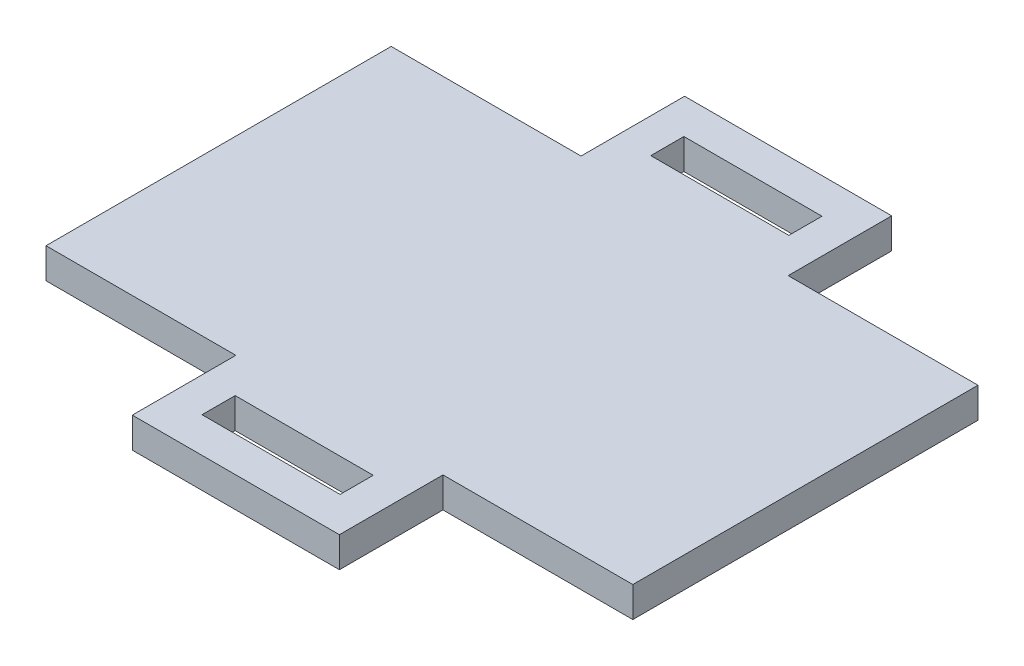
SolidWorks part; units mm, degrees
ref_plane "Front Plane" through (0, 0, 0) normal (0, 0, 1) x (1, 0, 0)
ref_plane "Top Plane" through (0, 0, 0) normal (0, 1, 0) x (1, 0, 0)
ref_plane "Right Plane" through (0, 0, 0) normal (1, 0, 0) x (0, 0, -1)
sketch "Sketch1" plane through (0, 0, 0) normal (0, 1, 0) x (1, 0, 0)
  line L0 (19.05, 31.75) -> (19.05, 50.8)
  line L1 (-53.975, -31.75) -> (-19.05, -31.75)
  line L2 (-53.975, -31.75) -> (-53.975, 31.75)
  line L3 (-53.975, 31.75) -> (-19.05, 31.75)
  line L4 (53.975, -31.75) -> (53.975, 31.75)
  line L5 (-53.975, -31.75) -> (53.975, 31.75) construction
  line L6 (-53.975, 31.75) -> (53.975, -31.75) construction
  line L7 (19.05, 50.8) -> (-19.05, 50.8)
  line L8 (-19.05, 50.8) -> (-19.05, 31.75)
  line L9 (19.05, 31.75) -> (53.975, 31.75)
  line L10 (-53.975, 0) -> (53.975, 0) construction
  line L11 (19.05, -31.75) -> (19.05, -50.8)
  line L12 (19.05, -50.8) -> (-19.05, -50.8)
  line L13 (-19.05, -50.8) -> (-19.05, -31.75)
  line L14 (19.05, -31.75) -> (53.975, -31.75)
  point P0 (0, 0)
  dimension "D1" = 107.95
  dimension "D2" = 63.5
  dimension "D3" = 19.05
  dimension "D4" = 38.1
extrude "Boss-Extrude1" add sketch "Sketch1" along normal blind 5.588
sketch "Sketch2" plane through (0, 5.588, 0) normal (0, 1, 0) x (1, 0, 0)
  line L0 (0, 0) -> (53.975, 0) construction
  line L1 (-12.7, 38.227) -> (12.7, 38.227)
  line L2 (-12.7, 38.227) -> (-12.7, 44.323)
  line L3 (-12.7, 44.323) -> (12.7, 44.323)
  line L4 (12.7, 38.227) -> (12.7, 44.323)
  line L5 (-12.7, 38.227) -> (12.7, 44.323) construction
  line L6 (-12.7, 44.323) -> (12.7, 38.227) construction
  line L7 (53.975, -31.75) -> (53.975, 31.75) construction
  line L8 (-12.7, -44.323) -> (12.7, -38.227) construction
  line L9 (-12.7, -38.227) -> (12.7, -44.323) construction
  line L10 (12.7, -38.227) -> (12.7, -44.323)
  line L11 (-12.7, -44.323) -> (12.7, -44.323)
  line L12 (-12.7, -38.227) -> (-12.7, -44.323)
  line L13 (-12.7, -38.227) -> (12.7, -38.227)
  point P0 (0, 41.275)
  point P5 (0, 0)
  point P15 (0, -41.275)
  dimension "D1" = 6.096
  dimension "D2" = 25.4
  dimension "D3" = 38.227
extrude "Cut-Extrude1" cut sketch "Sketch2" against normal through all
